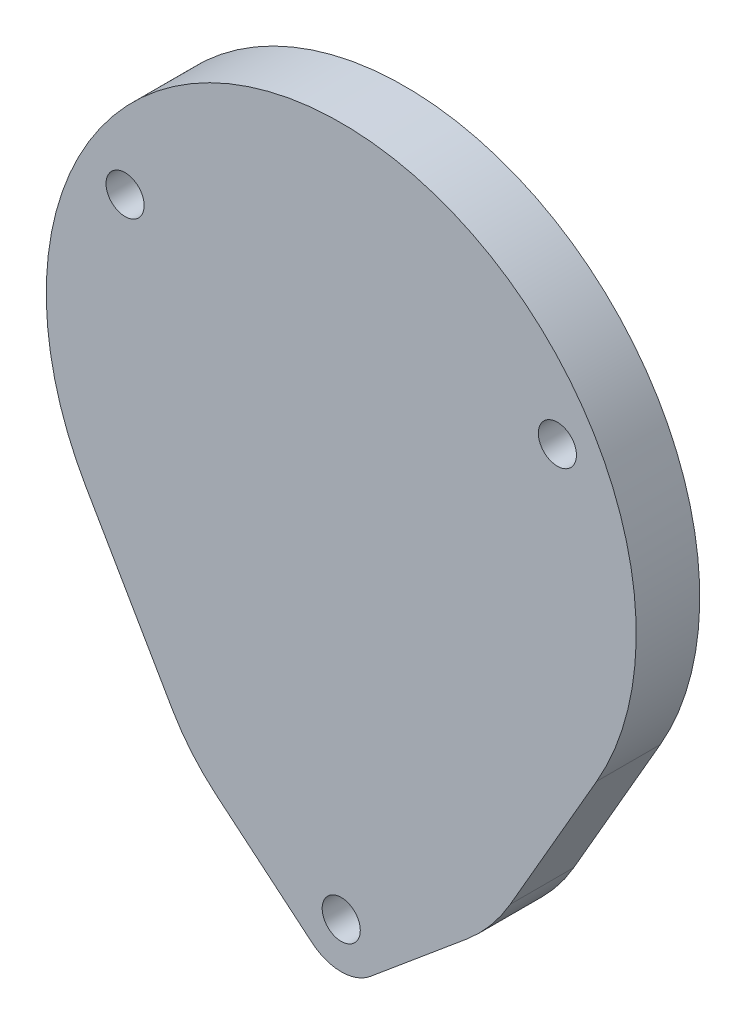
SolidWorks part; units mm, degrees
material "PET"
ref_plane "Front Plane" through (0, 0, 0) normal (0, 0, 1) x (1, 0, 0)
ref_plane "Top Plane" through (0, 0, 0) normal (0, 1, 0) x (1, 0, 0)
ref_plane "Right Plane" through (0, 0, 0) normal (1, 0, 0) x (0, 0, -1)
sketch "Sketch1" plane through (0, 0, 0) normal (0, 0, 1) x (1, 0, 0)
  line L0 (-28.1458, -16.25) -> (-18.6195, -32.75)
  line L1 (28.1458, -16.25) -> (18.6195, -32.75)
  line L2 (0, 0) -> (0, -22) construction
  line L3 (0, -22) -> (0, -43.5) construction
  line L4 (-3.2056, -47.3372) -> (-13.784, -38.5)
  line L5 (3.2056, -47.3372) -> (13.784, -38.5)
  line L6 (-23.8157, 13.75) -> (0, 0) construction
  line L7 (0, 0) -> (23.8157, 13.75) construction
  arc A0 (28.1458, -16.25) -> (-28.1458, -16.25) centre (0, 0) ccw
  arc A1 (-18.6195, -32.75) -> (-13.784, -38.5) centre (0, -22) ccw
  arc A2 (-3.2056, -47.3372) -> (3.2056, -47.3372) centre (0, -43.5) ccw
  arc A3 (13.784, -38.5) -> (18.6195, -32.75) centre (0, -22) ccw
  circle A4 centre (0, -43.5) radius 2.1
  circle A5 centre (-23.8157, 13.75) radius 2.1
  circle A6 centre (23.8157, 13.75) radius 2.1
  dimension "D1" = 65
  dimension "D2" = 22
  dimension "D3" = 43
  dimension "D4" = 10
  dimension "D5" = 4.2
  dimension "D6" = 4.2
  dimension "D7" = 4.2
  dimension "D10" = 5
  dimension "D11" = 5
  dimension "D8" = 120
  dimension "D9" = 120
extrude "Boss-Extrude1" add sketch "Sketch1" along normal blind 7
sketch "Sketch2" plane through (0, 0, 0) normal (0, 0, -1) x (-1, 0, 0)
  line L0 (-28.1458, -16.25) -> (-18.6195, -32.75) construction
  line L1 (-13.784, -38.5) -> (-3.2056, -47.3372) construction
  line L2 (3.2056, -47.3372) -> (13.784, -38.5) construction
  line L3 (18.6195, -32.75) -> (28.1458, -16.25) construction
  line L4 (-23.3827, -13.5) -> (-13.8564, -30)
  line L7 (13.8564, -30) -> (23.3827, -13.5)
  line L8 (-20.7846, -12) -> (-11.2583, -28.5)
  line L11 (11.2583, -28.5) -> (20.7846, -12)
  line L12 (-10.2579, -34.2791) -> (0, -42.8485) construction
  line L13 (0, -42.8485) -> (10.2579, -34.2791) construction
  line L14 (-8.3345, -31.9767) -> (0, -38.9394) construction
  line L15 (0, -38.9394) -> (8.3345, -31.9767) construction
  arc A0 (28.1458, -16.25) -> (-28.1458, -16.25) centre (0, 0) ccw construction
  arc A1 (-3.2056, -47.3372) -> (3.2056, -47.3372) centre (0, -43.5) ccw construction
  arc A2 (-18.6195, -32.75) -> (-13.784, -38.5) centre (0, -22) ccw construction
  arc A3 (13.784, -38.5) -> (18.6195, -32.75) centre (0, -22) ccw construction
  arc A4 (23.3827, -13.5) -> (24.327, 11.7132) centre (0, 0) ccw
  arc A5 (-13.8564, -30) -> (10.2579, -34.2791) centre (0, -22) ccw
  arc A6 (0, -42.8485) -> (0, -42.8485) centre (0, -42.8485) ccw
  arc A7 (10.2579, -34.2791) -> (13.8564, -30) centre (0, -22) ccw
  arc A8 (20.7846, -12) -> (-20.7846, -12) centre (0, 0) ccw
  arc A9 (-11.2583, -28.5) -> (8.3345, -31.9767) centre (0, -22) ccw
  arc A10 (-11.2583, -28.5) -> (-8.3345, -31.9767) centre (0, -22) ccw construction
  arc A11 (8.3345, -31.9767) -> (11.2583, -28.5) centre (0, -22) ccw
  arc A12 (-24.327, 11.7132) -> (-22.3074, 15.2112) centre (-23.8157, 13.75) ccw
  arc A13 (22.3074, 15.2112) -> (24.327, 11.7132) centre (23.8157, 13.75) ccw
  arc A15 (-24.327, 11.7132) -> (-23.3827, -13.5) centre (0, 0) ccw
  arc A16 (23.3827, -13.5) -> (-23.3827, -13.5) centre (0, 0) ccw construction
  arc A17 (22.3074, 15.2112) -> (-22.3074, 15.2112) centre (0, 0) ccw
  arc A18 (0, -38.9394) -> (0, -38.9394) centre (0, -38.9394) ccw construction
  arc A19 (-13.8564, -30) -> (-10.2579, -34.2791) centre (0, -22) ccw construction
  circle M18 centre (0, -43.5) radius 2.1
  circle M19 centre (23.8157, 13.75) radius 2.1
  circle M20 centre (-23.8157, 13.75) radius 2.1
  dimension "D3" = 4.2
  dimension "D5" = 4.2
  dimension "D1" = 5.5
  dimension "D2" = 3
extrude "Boss-Extrude2" add sketch "Sketch2" along normal blind 2 contours A17 A15 L4 A5 A7 L7 A4 A11 A9 L8 A8 L11 M19 M20 M18 region at (26.1366, -0.9789, 0)
sketch "Sketch3" plane through (0, 0, 0) normal (0, 0, -1) x (-1, 0, 0)
  circle A0 centre (0, -22) radius 7.05
  dimension "D1" = 14.1
extrude "Cut-Extrude1" cut sketch "Sketch3" against normal blind 5
